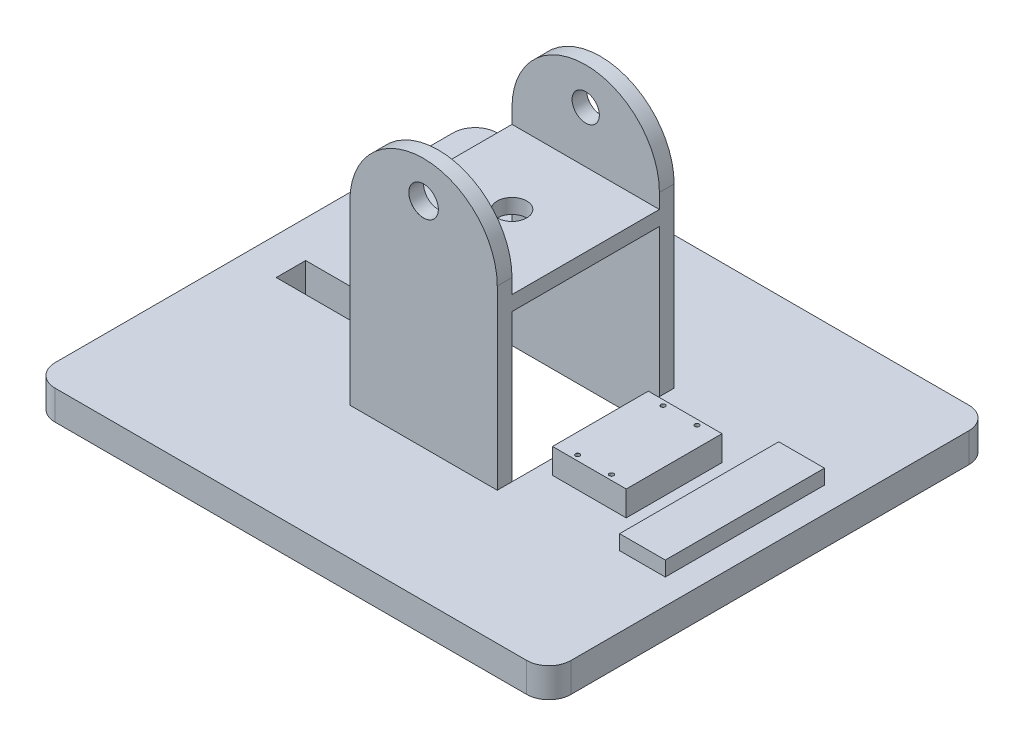
SolidWorks part; units mm, degrees
ref_plane "Front Plane" through (0, 0, 0) normal (0, 0, 1) x (1, 0, 0)
ref_plane "Top Plane" through (0, 0, 0) normal (0, 1, 0) x (1, 0, 0)
ref_plane "Right Plane" through (0, 0, 0) normal (1, 0, 0) x (0, 0, -1)
sketch "Sketch1" plane through (0, 0, 0) normal (0, 1, 0) x (1, 0, 0)
  line L1 (0, 0) -> (350, 0)
  line L2 (0, 0) -> (0, -300)
  line L3 (0, -300) -> (350, -300)
  line L4 (350, 0) -> (350, -300)
  dimension "D1" = 350
  dimension "D2" = 300
extrude "Boss-Extrude1" add sketch "Sketch1" along normal blind 20
fillet "Fillet1" radius 15 4 edges at (350, 10, 0) (0, 10, 0) (0, 10, 300) (350, 10, 300)
sketch "Sketch2" plane through (0, 20, 0) normal (0, 1, 0) x (1, 0, 0)
  line L0 (335, 0) -> (15, 0) construction
  line L1 (125, -100) -> (225, -100)
  line L2 (125, -100) -> (125, -200)
  line L3 (125, -200) -> (225, -200)
  line L4 (225, -100) -> (225, -200)
  line L8 (175, -100) -> (175, 0) construction
  line L9 (175, -200) -> (175, -300) construction
  line L10 (15, -300) -> (335, -300) construction
  line L11 (125, -150) -> (0, -150) construction
  line L12 (0, -15) -> (0, -285) construction
  line L13 (225, -150) -> (350, -150) construction
  line L14 (350, -285) -> (350, -15) construction
  dimension "D2" = 100
  dimension "D1" = 100
extrude "Cut-Extrude1" cut sketch "Sketch2" against normal blind 20 contours L1 L4 L3 L2
sketch "Sketch6" plane through (0, 0, 100) normal (0, 0, 1) x (1, 0, 0)
  line L0 (125, 0) -> (125, 140)
  line L1 (225, 140) -> (225, 0)
  line L2 (15, 0) -> (335, 0) construction
  line L3 (125, 140) -> (225, 140) construction
  line L4 (125, 0) -> (225, 0)
  arc A0 (125, 140) -> (225, 140) centre (175, 140) cw
  dimension "D1" = 100
  dimension "D2" = 140
extrude "Boss-Extrude2" add sketch "Sketch6" against normal blind 10
pattern_linear "LPattern1" count 2 spacing 110 along (0, 0, 1) of "Boss-Extrude2"
sketch "Sketch23" plane through (0, 0, 210) normal (0, 0, 1) x (1, 0, 0)
  line L0 (125, 140) -> (225, 140) construction
  line L1 (225, 140) -> (175, 140) construction
  line L2 (175, 140) -> (175, 190) construction
  line L3 (175, 190) -> (175, 165) construction
  line L4 (175, 165) -> (218.3013, 165) construction
  arc A0 (225, 140) -> (125, 140) centre (175, 140) ccw construction
hole_wizard "Ø20.0 (20) Diameter Hole2" positions "Sketch24" profile "Sketch25" hole size "Ø20.0" standard "ANSI Metric"
sketch "Sketch24" plane through (0, 0, 210) normal (0, 0, 1) x (1, 0, 0)
  point P0 (175, 165)
sketch "Sketch25" plane through (175, 165, 210) normal (1, 0, 0) x (0, -1, 0)
  line L0 (0, 0) -> (0, 16.0086)
  line L1 (0, 16.0086) -> (10, 10)
  line L2 (10, 10) -> (10, 0.025)
  line L3 (10, 0.025) -> (10.025, 0)
  line L5 (10.025, 0) -> (0, 0)
  line L6 (-10, 0.025) -> (-10.025, 0) construction
  line L10 (0, 16.0086) -> (-10, 10) construction
  line L11 (0, -6.35) -> (0, 107.95) construction
  dimension "Hole Dia." = 20
  dimension "Hole Depth" = 10
  dimension "Near C'Sink Dia." = 20.05
  dimension "Near C'Sink Angle" = 90
  dimension "Drill Angle" = 118
hole_wizard "Ø18.5 (18.5) Diameter Hole1" positions "Sketch29" profile "Sketch30" hole size "Ø18.5" standard "ANSI Metric"
sketch "Sketch29" plane through (0, 0, 90) normal (0, 0, -1) x (-1, 0, 0)
  point P0 (-175, 165)
sketch "Sketch30" plane through (175, 165, 90) normal (1, 0, 0) x (0, 1, 0)
  line L0 (0, 0) -> (0, 15.558)
  line L1 (0, 15.558) -> (9.25, 10)
  line L2 (9.25, 10) -> (9.25, 0.025)
  line L3 (9.25, 0.025) -> (9.275, 0)
  line L5 (9.275, 0) -> (0, 0)
  line L6 (-9.25, 0.025) -> (-9.275, 0) construction
  line L10 (0, 15.558) -> (-9.25, 10) construction
  line L11 (0, -6.35) -> (0, 107.95) construction
  dimension "Hole Dia." = 18.5
  dimension "Hole Depth" = 10
  dimension "Near C'Sink Dia." = 18.55
  dimension "Near C'Sink Angle" = 90
  dimension "Drill Angle" = 118
sketch "Sketch32" plane through (0, 0, 210) normal (0, 0, 1) x (1, 0, 0)
  line L0 (125, 140) -> (125, 20) construction
  line L16 (125, 130) -> (225, 130)
  line L17 (125, 130) -> (125, 120)
  line L18 (125, 120) -> (225, 120)
  line L19 (225, 130) -> (225, 120)
  line L20 (225, 20) -> (225, 140) construction
  line L21 (225, 20) -> (125, 20) construction
  dimension "D1" = 100
extrude "Boss-Extrude3" add sketch "Sketch32" against normal blind 120
sketch "Sketch37" plane through (0, 130, 0) normal (0, 1, 0) x (1, 0, 0)
  line L0 (175, -90) -> (175, -210) construction
  line L1 (225, -90) -> (125, -90) construction
  line L2 (125, -210) -> (225, -210) construction
  line L3 (175, -210) -> (175, -150) construction
  line L4 (175, -150) -> (225, -150) construction
  line L5 (225, -100) -> (225, -200) construction
  line L6 (225, -150) -> (125, -150) construction
  line L7 (125, -100) -> (125, -200) construction
  circle A0 centre (175, -150) radius 10
  dimension "D1" = 20
extrude "Cut-Extrude2" cut sketch "Sketch37" against normal blind 36.0783
sketch "Sketch45" plane through (0, 20, 0) normal (0, 1, 0) x (1, 0, 0)
  line L0 (260, -117.5) -> (260, 0) construction
  line L1 (245, -117.5) -> (275, -117.5)
  line L2 (245, -117.5) -> (245, -182.5)
  line L3 (245, -182.5) -> (275, -182.5)
  line L4 (275, -117.5) -> (275, -182.5)
  line L5 (335, 0) -> (15, 0) construction
  line L6 (260, -182.5) -> (260, -300) construction
  line L7 (15, -300) -> (335, -300) construction
  line L8 (350, -285) -> (350, -15) construction
  line L12 (275, -117.5) -> (285, -117.5)
  line L13 (275, -117.5) -> (275, -182.5)
  line L14 (275, -182.5) -> (285, -182.5)
  line L15 (285, -117.5) -> (285, -182.5)
  line L16 (245, -117.5) -> (235, -117.5)
  line L17 (245, -117.5) -> (245, -182.5)
  line L18 (245, -182.5) -> (235, -182.5)
  line L19 (235, -117.5) -> (235, -182.5)
  dimension "D1" = 65
  dimension "D2" = 30
  dimension "D3" = 75
  dimension "D4" = 10
extrude "Boss-Extrude4" add sketch "Sketch45" along normal blind 17 contours L4 L3 L2 L1
hole_wizard "M2.5 Clearance Hole1" positions "Sketch50" profile "Sketch51" hole size "M2.5" standard "ISO"
sketch "Sketch50" plane through (0, 37, 0) normal (0, 1, 0) x (1, 0, 0)
  line L0 (245, -117.5) -> (275, -117.5) construction
  line L1 (245, -117.5) -> (245, -182.5) construction
  line L2 (245, -117.5) -> (275, -117.5) construction
  line L3 (275, -117.5) -> (275, -182.5) construction
  line L4 (245, -182.5) -> (275, -182.5) construction
  point P0 (248.5, -121)
  point P2 (271.5, -121)
  point P3 (271.5, -179)
  point P5 (248.5, -179)
  dimension "D1" = 3.5
  dimension "D2" = 3.5
  dimension "D3" = 3.5
  dimension "D4" = 3.5
  dimension "D5" = 3.5
  dimension "D6" = 3.5
  dimension "D7" = 3.5
  dimension "D8" = 3.5
sketch "Sketch51" plane through (248.5, 37, 121) normal (1, 0, 0) x (0, 0, 1)
  line L0 (0, 0) -> (0, 13.2712)
  line L1 (0, 13.2712) -> (1.45, 12.4)
  line L2 (1.45, 12.4) -> (1.45, 0.025)
  line L3 (1.45, 0.025) -> (1.475, 0)
  line L5 (1.475, 0) -> (0, 0)
  line L6 (-1.45, 0.025) -> (-1.475, 0) construction
  line L10 (0, 13.2712) -> (-1.45, 12.4) construction
  line L11 (0, -6.35) -> (0, 107.95) construction
  dimension "Hole Dia." = 2.9
  dimension "Hole Depth" = 12.4
  dimension "Near C'Sink Dia." = 2.95
  dimension "Near C'Sink Angle" = 90
  dimension "Drill Angle" = 118
sketch "Sketch54" plane through (0, 20, 0) normal (0, 1, 0) x (1, 0, 0)
  line L1 (275, -117.5) -> (285, -117.5)
  line L2 (275, -117.5) -> (275, -182.5)
  line L3 (275, -182.5) -> (285, -182.5)
  line L4 (285, -117.5) -> (285, -182.5)
  line L5 (245, -117.5) -> (235, -117.5)
  line L6 (245, -117.5) -> (245, -182.5)
  line L7 (245, -182.5) -> (235, -182.5)
  line L8 (235, -117.5) -> (235, -182.5)
  dimension "D1" = 10
extrude "Boss-Extrude5" add sketch "Sketch54" along normal blind 17
sketch "Sketch55" plane through (0, 20, 0) normal (0, 1, 0) x (1, 0, 0)
  line L0 (317.5, -96) -> (317.5, 0) construction
  line L1 (302, -96) -> (333, -96)
  line L2 (302, -96) -> (302, -204)
  line L3 (302, -204) -> (333, -204)
  line L4 (333, -96) -> (333, -204)
  line L5 (335, 0) -> (15, 0) construction
  line L6 (317.5, -204) -> (317.5, -300) construction
  line L7 (15, -300) -> (335, -300) construction
  line L8 (333, -150) -> (350, -150) construction
  line L9 (350, -285) -> (350, -15) construction
  line L10 (302, -150) -> (285, -150) construction
  line L12 (285, -182.5) -> (285, -117.5) construction
  dimension "D1" = 108
  dimension "D2" = 31
extrude "Boss-Extrude6" add sketch "Sketch55" along normal blind 10
sketch "Sketch59" plane through (0, 20, 0) normal (0, 1, 0) x (1, 0, 0)
  line L0 (65, -140) -> (65, 0) construction
  line L1 (25, -140) -> (105, -140)
  line L2 (25, -140) -> (25, -160)
  line L3 (25, -160) -> (105, -160)
  line L4 (105, -140) -> (105, -160)
  line L5 (335, 0) -> (15, 0) construction
  line L6 (65, -160) -> (65, -300) construction
  line L7 (15, -300) -> (335, -300) construction
  line L8 (0, -15) -> (0, -285) construction
  dimension "D1" = 20
  dimension "D2" = 80
  dimension "D3" = 25
extrude "Cut-Extrude3" cut sketch "Sketch59" against normal through all contours L1 L4 L3 L2
equation "\"bar_width\"=100"
equation "\"D2@Sketch2\"=\"bar_width\""
equation "\"bar_length\"=100"
equation "\"D1@Sketch2\"=\"bar_length\""
equation "\"D1@Boss-Extrude3\"=\"bar_length\" + 20mm"
equation "\"tower-height\"=100"
equation "\"D1@Sketch32\"=\"tower-height\""
equation "\"lens_diameter\"=20"
equation "\"D1@Sketch37\"=\"lens_diameter\""
equation "\"R_pi_length\"=65"
equation "\"D1@Sketch45\"=\"R_pi_length\""
equation "\"R_pi_width\"=30"
equation "\"D2@Sketch45\"=\"R_pi_width\""
equation "\"RP_tappings\"=3.5"
equation "\"D1@Sketch50\"=\"RP_tappings\""
equation "\"R_pi_height\"=10"
equation "\"Single_battery_width\"= 31mm"
equation "\"D2@Sketch55\"=\"Single_battery_width\""
